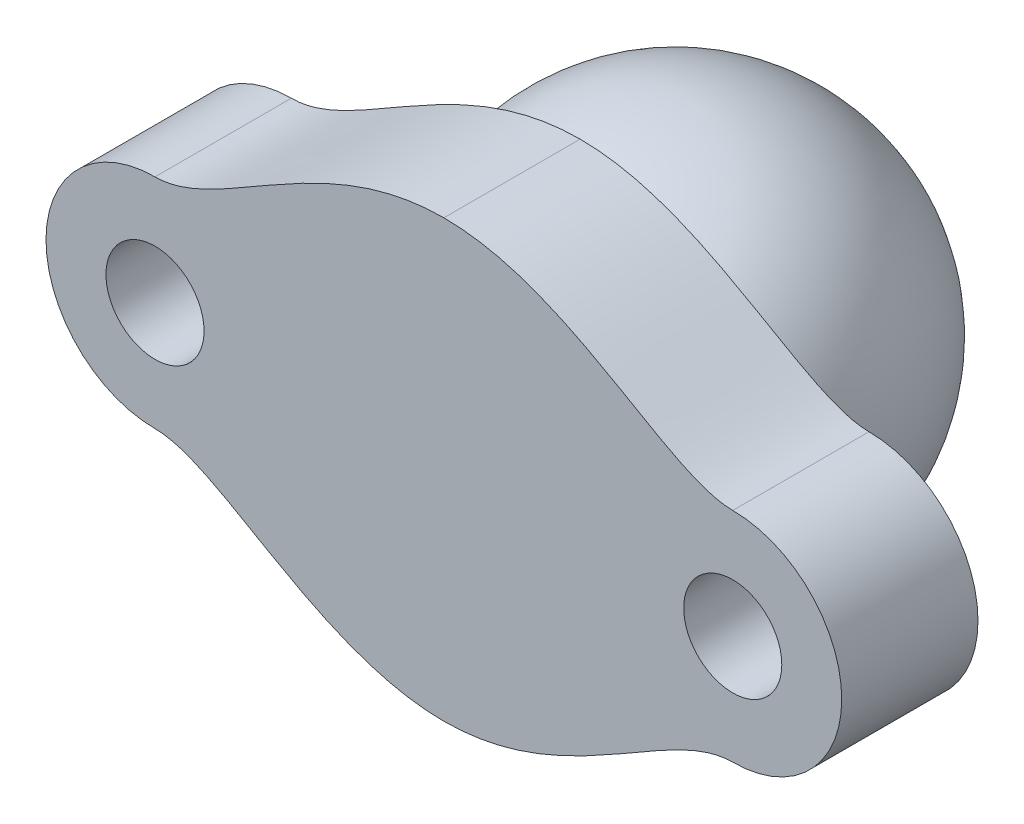
SolidWorks part; units mm, degrees
ref_plane "Front Plane" through (0, 0, 0) normal (0, 0, 1) x (1, 0, 0)
ref_plane "Top Plane" through (0, 0, 0) normal (0, 1, 0) x (1, 0, 0)
ref_plane "Right Plane" through (0, 0, 0) normal (1, 0, 0) x (0, 0, -1)
sketch "Sketch1" plane through (0, 0, 0) normal (0, 0, 1) x (1, 0, 0)
  line L0 (0, 5.08) -> (0, -5.08) construction
  line L1 (-9.271, 0) -> (9.271, 0) construction
  arc A0 (-6.731, -2.54) -> (-6.731, 2.54) centre (-6.731, 0) cw
  circle A1 centre (6.731, 0) radius 1.143
  arc A2 (6.731, -2.54) -> (6.731, 2.54) centre (6.731, 0) ccw
  circle A3 centre (-6.731, 0) radius 1.143
  spline S0 degree 3 poles (6.731, 2.54) (5.1875, 2.54) (2.9211, 5.0802) (0, 5.08) knots 0 0 0 0 1 1 1 1
  spline S1 degree 3 poles (6.731, -2.54) (5.1875, -2.54) (2.9211, -5.0802) (0, -5.08) knots 0 0 0 0 1 1 1 1
  spline S2 degree 3 poles (-6.731, -2.54) (-5.1875, -2.54) (-2.9211, -5.0802) (0, -5.08) knots 0 0 0 0 1 1 1 1
  spline S3 degree 3 poles (-6.731, 2.54) (-5.1875, 2.54) (-2.9211, 5.0802) (0, 5.08) knots 0 0 0 0 1 1 1 1
  point P13 (0, 0)
  dimension "D2" = 2.286
  dimension "D4" = 5.08
  dimension "D3" = 6.731
extrude "Boss-Extrude1" add sketch "Sketch1" along normal blind 3.175 contours A2
sketch "Sketch4" plane through (0, 0, 0) normal (0, 1, 0) x (1, 0, 0)
  line L0 (0, 0) -> (4.2121, 0)
  line L1 (0, 0) -> (0, 6.985)
  arc A0 (4.2121, 0) -> (0, 6.985) centre (0, 2.2225) ccw
  point P3 (0, 6.985)
  dimension "D1" = 9.525
  dimension "D2" = 10.16
revolve "Revolve1" add sketch "Sketch4" angle 360 about L1
